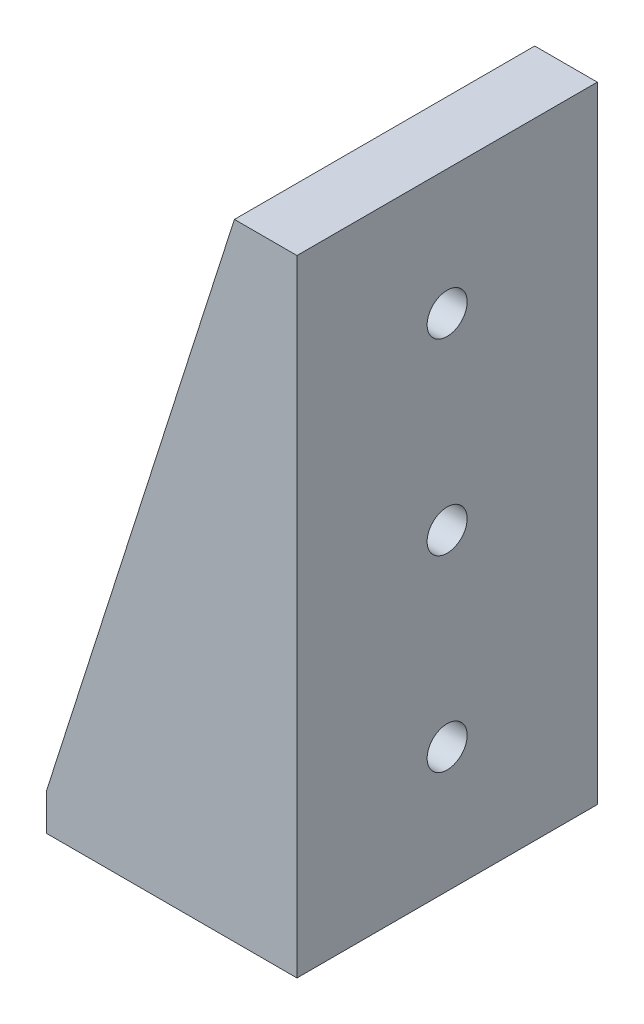
SolidWorks part; units mm, degrees
ref_plane "Front Plane" through (0, 0, 0) normal (0, 0, 1) x (1, 0, 0)
ref_plane "Top Plane" through (0, 0, 0) normal (0, 1, 0) x (1, 0, 0)
ref_plane "Right Plane" through (0, 0, 0) normal (1, 0, 0) x (0, 0, -1)
sketch "Sketch1" plane through (0, 0, 0) normal (0, 0, 1) x (1, 0, 0)
  line L0 (-10, 0) -> (10, 0)
  line L1 (-10, 0) -> (-10, 3)
  line L2 (-10, 3) -> (5, 50)
  line L3 (-10, 3) -> (23.3287, 3) construction
  line L4 (5, 50) -> (10, 50)
  line L5 (10, 0) -> (10, 50)
  point P4 (0, 0)
  dimension "D1" = 20
  dimension "D2" = 3
  dimension "D3" = 50
  dimension "D4" = 5
extrude "Boss-Extrude1" add sketch "Sketch1" along normal blind 24
sketch "Sketch3" plane through (-9.9445, 3.1738, 0) normal (-0.9527, 0.304, 0) x (0, 0, 1)
  line L0 (2.5, 49.1532) -> (2.5, -0.1824)
  line L1 (2.5, -0.1824) -> (17.5, -0.1824)
  line L2 (17.5, -0.1824) -> (17.5, 49.1532)
  line L4 (24, -0.1824) -> (0, -0.1824) construction
  line L5 (2.5, 49.1532) -> (17.5, 49.1532)
  line L6 (24, 49.1532) -> (0, 49.1532) construction
ref_plane "Plane1" through (-10, 0, 0) normal (-1, 0, 0) x (0, 0, 1)
sketch "Sketch4" plane through (-10, 0, 0) normal (-1, 0, 0) x (0, 0, 1)
  line L4 (2.5, 50) -> (2.5, 2.9986)
  line L5 (21.5, 2.9986) -> (21.5, 50)
  line L6 (2.5, 2.9986) -> (21.5, 2.9986)
  line L7 (2.5, 50) -> (21.5, 50)
  line L10 (24, 50) -> (0, 50) construction
  line L11 (24, 0) -> (0, 0) construction
  dimension "D1" = 2.5
  dimension "D2" = 2.5
  dimension "D3" = 2.9986
extrude "Cut-Extrude2" cut sketch "Sketch4" against normal up to vertex (15 mm away) up to point (5, 50, 2.5)
sketch "Sketch6" plane through (10, 0, 0) normal (1, 0, 0) x (0, 0, -1)
  line L0 (0, 10) -> (-24, 10) construction
  line L3 (0, 0) -> (0, 50) construction
  line L6 (-24, 0) -> (-24, 50) construction
  line L7 (0, 25) -> (-24, 25) construction
  line L8 (0, 40) -> (-24, 40) construction
  circle A0 centre (-12, 25) radius 1.6
  circle A1 centre (-12, 10) radius 1.6
  circle A2 centre (-12, 40) radius 1.6
  dimension "D1" = 3.2
  dimension "D4" = 3.2
  dimension "D5" = 3.2
  dimension "D2" = 15
  dimension "D3" = 15
extrude "Cut-Extrude4" cut sketch "Sketch6" against normal up to surface (5 mm away) up to face at (5, 26.4993, 12)
sketch "Sketch7" plane through (0, 2.9986, 0) normal (0, 1, 0) x (1, 0, 0)
  line L0 (-10, -12) -> (8, -12) construction
  line L3 (-7, -12) -> (3, -12) construction
  line L4 (-7, -11) -> (3, -11)
  line L5 (-7, -13) -> (3, -13)
  line L7 (-10, 0) -> (10, 0) construction
  arc A0 (-7, -11) -> (-7, -13) centre (-7, -12) ccw
  arc A1 (3, -13) -> (3, -11) centre (3, -12) ccw
  point P8 (-2, -12)
  dimension "D1" = 1
  dimension "D3" = 5
  dimension "D2" = 3
  dimension "D4" = 12
  dimension "D5" = 18
extrude "Cut-Extrude5" cut sketch "Sketch7" against normal up to surface (2.9986 mm away) up to face at (0, 0, 12)
fillet "Fillet1" radius 1 3 edges at (5, 2.9986, 12) (-2.5, 2.9986, 21.5) (-2.5, 2.9986, 2.5)
